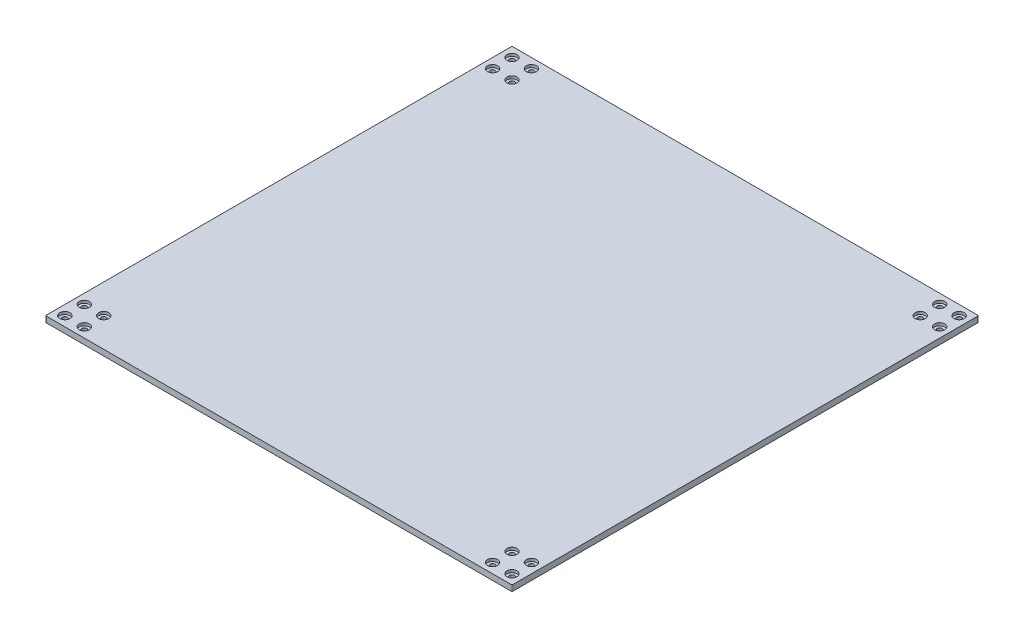
SolidWorks part; units mm, degrees
material "ASTM A36 Steel"
ref_plane "Front Plane" through (0, 0, 0) normal (0, 0, 1) x (1, 0, 0)
ref_plane "Top Plane" through (0, 0, 0) normal (0, 1, 0) x (1, 0, 0)
ref_plane "Right Plane" through (0, 0, 0) normal (1, 0, 0) x (0, 0, -1)
sketch "Sketch1" plane through (0, 0, 0) normal (0, 1, 0) x (1, 0, 0)
  line L1 (240, -240) -> (-240, -240)
  line L2 (240, -240) -> (240, 240)
  line L3 (240, 240) -> (-240, 240)
  line L4 (-240, -240) -> (-240, 240)
  line L5 (240, -240) -> (-240, 240) construction
  line L6 (240, 240) -> (-240, -240) construction
  point P0 (0, 0)
  dimension "D1" = 480
extrude "Boss-Extrude1" add sketch "Sketch1" along normal blind 6
sketch "Sketch2" plane through (0, 6, 0) normal (0, 1, 0) x (1, 0, 0)
  line L1 (-200, 200) -> (-240, 200)
  line L2 (-200, 200) -> (-200, 240)
  line L3 (-200, 240) -> (-240, 240)
  line L4 (-240, 200) -> (-240, 240)
  line L5 (-200, 200) -> (-240, 240) construction
  line L6 (-200, 240) -> (-240, 200) construction
  line L7 (-210, 210) -> (-230, 210)
  line L8 (-210, 210) -> (-210, 230)
  line L9 (-210, 230) -> (-230, 230)
  line L10 (-230, 210) -> (-230, 230)
  line L11 (-210, 210) -> (-230, 230) construction
  line L12 (-210, 230) -> (-230, 210) construction
  point P0 (-220, 220)
  point P6 (-220, 220)
  dimension "D1" = 40
  dimension "D2" = 20
hole_wizard "CBORE for M5 SBHCS1" positions "Sketch5" profile "Sketch6" counterbore size "M5" standard "ANSI Metric" end condition through all
sketch "Sketch5" plane through (0, 6, 0) normal (0, 1, 0) x (1, 0, 0)
  point P0 (-230, 230)
  point P3 (-210, 230)
  point P6 (-210, 210)
  point P9 (-230, 210)
sketch "Sketch6" plane through (-230, 6, -230) normal (1, 0, 0) x (0, 0, 1)
  line L0 (0, 0) -> (0, 6)
  line L1 (0, 6) -> (2.65, 6)
  line L3 (2.65, 6) -> (2.65, 2.75)
  line L4 (2.65, 2.75) -> (5.25, 2.75)
  line L5 (5.25, 2.75) -> (5.25, 0)
  line L7 (5.25, 0) -> (0, 0)
  line L11 (0, -6.35) -> (0, 107.95) construction
  dimension "Thru Hole Dia." = 5.3
  dimension "Thru Hole Depth" = 6
  dimension "C'Bore Dia." = 10.5
  dimension "C'Bore Depth" = 2.75
sketch "Sketch9" plane through (0, 6, 0) normal (0, 1, 0) x (1, 0, 0)
  line L0 (-230, 210) -> (-210, 230) construction
  line L1 (-154.5, 154.5) -> (-227.5, 154.5)
  line L2 (-154.5, 154.5) -> (-154.5, 227.5)
  line L3 (-154.5, 227.5) -> (-227.5, 227.5)
  line L4 (-227.5, 154.5) -> (-227.5, 227.5)
  line L5 (-154.5, 154.5) -> (-227.5, 227.5) construction
  line L6 (-154.5, 227.5) -> (-227.5, 154.5) construction
  line L7 (-162, 162) -> (-220, 162)
  line L8 (-162, 162) -> (-162, 220)
  line L9 (-162, 220) -> (-220, 220)
  line L10 (-220, 162) -> (-220, 220)
  line L11 (-162, 162) -> (-220, 220) construction
  line L12 (-162, 220) -> (-220, 162) construction
  point P0 (-191, 191)
  point P5 (-191, 191)
  dimension "D1" = 73
  dimension "D2" = 58
ref_axis "Axis1" through (0, 8.4, 0) along (0, -1, 0)
pattern_circular "CirPattern1" count 4 over 360 about axis through (0, 8.4, 0) along (0, -1, 0) of "CBORE for M5 SBHCS1"
fillet "Fillet1" radius 1 4 edges at (-240, 3, -240) (240, 3, -240) (240, 3, 240) (-240, 3, 240)
